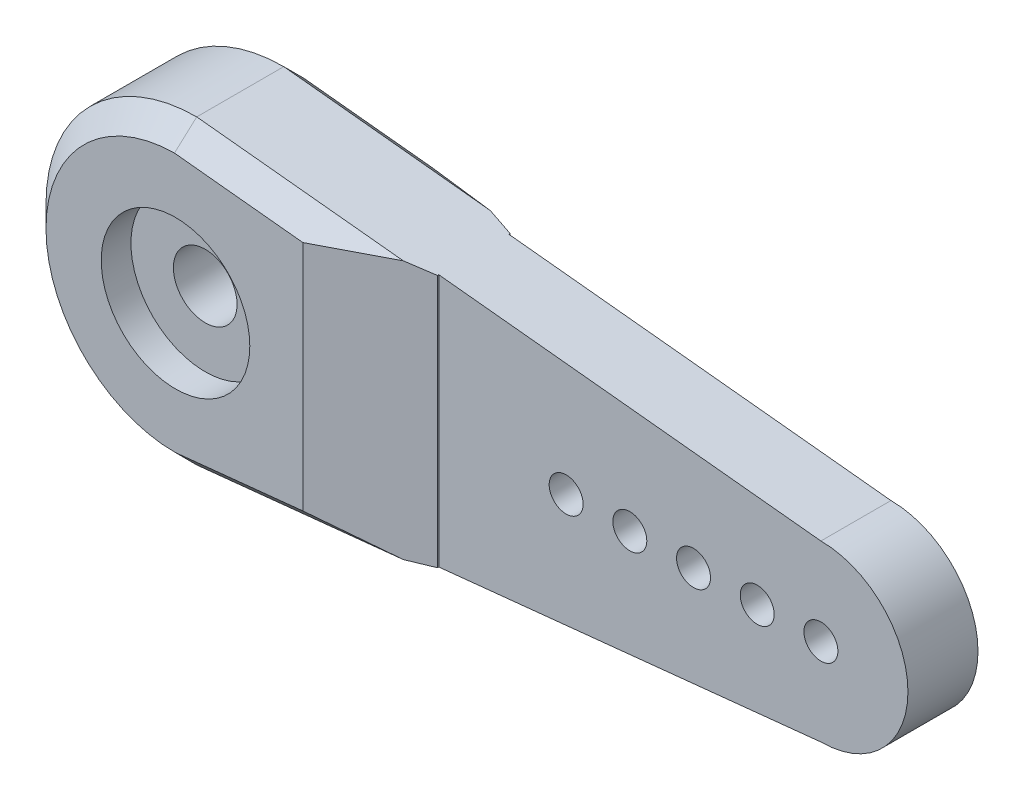
SolidWorks part; units mm, degrees
ref_plane "Plan de face" through (0, 0, 0) normal (0, 0, 1) x (1, 0, 0)
ref_plane "Plan de dessus" through (0, 0, 0) normal (0, 1, 0) x (1, 0, 0)
ref_plane "Plan de droite" through (0, 0, 0) normal (1, 0, 0) x (0, 0, -1)
sketch "Esquisse1" plane through (0, 0, 0) normal (0, 0, 1) x (1, 0, 0)
  line L0 (0, 7.1) -> (0, -7.1) construction
  line L1 (0, -7.1) -> (29, -4.1)
  line L2 (29, -4.1) -> (29, 4.1) construction
  line L3 (29, 4.1) -> (0, 7.1)
  line L4 (-10.867, 0) -> (29.1945, 0) construction
  arc A0 (0, 7.1) -> (0, -7.1) centre (0, 0) ccw
  arc A1 (29, 4.1) -> (29, -4.1) centre (29, 0) cw
  circle A2 centre (29, 0) radius 0.8
  circle A3 centre (26, 0) radius 0.8
  circle A4 centre (23, 0) radius 0.8
  circle A5 centre (20, 0) radius 0.8
  circle A6 centre (17, 0) radius 0.8
  circle A7 centre (0, 0) radius 1.5
  dimension "D1" = 7.1
  dimension "D2" = 4.1
  dimension "D4" = 1.6
  dimension "D6" = 3
  dimension "D3" = 29
  dimension "D5" = 5
extrude "Boss.-Extru.1" add sketch "Esquisse1" along normal blind 3.3
sketch "Esquisse2" plane through (0, 0, 3.3) normal (0, 0, 1) x (1, 0, 0)
  line L0 (29, 4.1) -> (0, 7.1) construction
  line L1 (0, -7.1) -> (11, -5.9621)
  line L2 (0, -7.1) -> (29, -4.1) construction
  line L3 (11, -5.9621) -> (11, 5.9621)
  line L4 (11, 5.9621) -> (0, 7.1)
  arc A0 (0, 7.1) -> (0, -7.1) centre (0, 0) ccw
  arc A1 (0, 7.1) -> (0, -7.1) centre (0, 0) ccw construction
  circle A2 centre (0, 0) radius 3.5
  dimension "D2" = 7
  dimension "D1" = 11
extrude "Boss.-Extru.2" add sketch "Esquisse2" along normal blind 1.4 and the other way blind 4.7
chamfer "Chanfrein1" distance 5 angle 15 2 edges at (11, 0, 4.7) (11, 0, -1.4)
chamfer "Chanfrein3" distance 1 angle 45 4 edges at (-7.1, 0, -1.4) (3, 6.7897, -1.4) (-7.1, 0, 4.7) (3, 6.7897, 4.7)
